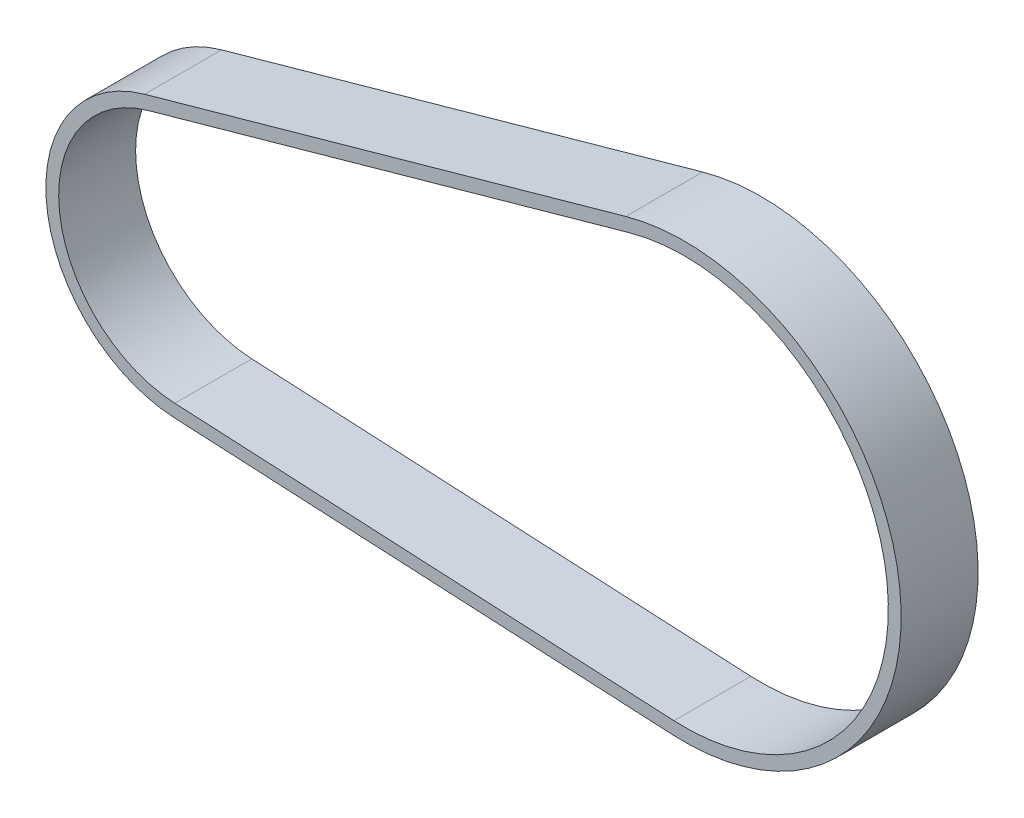
SolidWorks part; units mm, degrees
ref_plane "Front Plane" through (0, 0, 0) normal (0, 0, 1) x (1, 0, 0)
ref_plane "Top Plane" through (0, 0, 0) normal (0, 1, 0) x (1, 0, 0)
ref_plane "Right Plane" through (0, 0, 0) normal (1, 0, 0) x (0, 0, -1)
sketch "Sketch2" plane through (0, 0, 0) normal (0, 0, 1) x (1, 0, 0)
  line L0 (0, 0) -> (1, 0) construction
  line L1 (0, 0) -> (0, 1) construction
  line L2 (57.6509, -17.2737) -> (-0.7274, -14.3055)
  line L3 (-3.863, 13.7932) -> (52.4248, 29.5574)
  arc A0 (52.4248, 29.5574) -> (57.6509, -17.2737) centre (58.8631, 6.5687) cw
  arc A1 (-0.7274, -14.3055) -> (-3.863, 13.7932) centre (0, 0) cw
extrude "Extrude-Thin1" add sketch "Sketch2" against normal blind 9 thin thin type one direction wall 1.5
